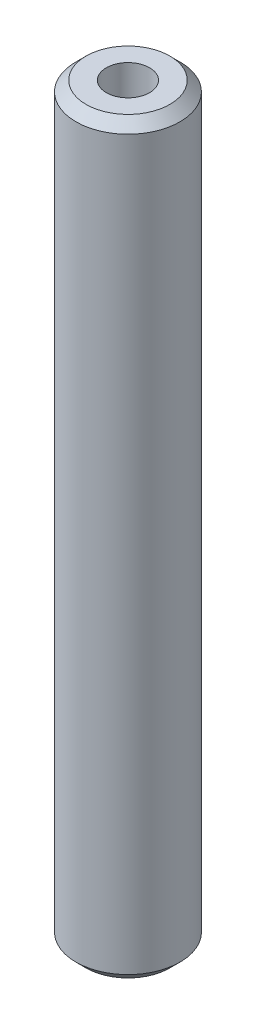
SolidWorks part; units mm, degrees
ref_plane "Front Plane" through (0, 0, 0) normal (0, 0, 1) x (1, 0, 0)
ref_plane "Top Plane" through (0, 0, 0) normal (0, 1, 0) x (1, 0, 0)
ref_plane "Right Plane" through (0, 0, 0) normal (1, 0, 0) x (0, 0, -1)
sketch "Sketch1" plane through (0, 0, 0) normal (0, 1, 0) x (1, 0, 0)
  circle A0 centre (0, 0) radius 12.5
  dimension "SHAFT_OD" = 25
extrude "Boss-Extrude1" add sketch "Sketch1" along normal blind 179.8903
sketch "Sketch2" plane through (0, 0, 0) normal (0, 1, 0) x (1, 0, 0)
  circle A0 centre (0, 0) radius 5.203
  dimension "BORE_D" = 10.406
extrude "Cut-Extrude1" cut sketch "Sketch2" along normal through all
chamfer "Chamfer1" distance 2.4188 angle 45 2 edges at (0, 179.8903, 12.5) (0, 0, 12.5)
